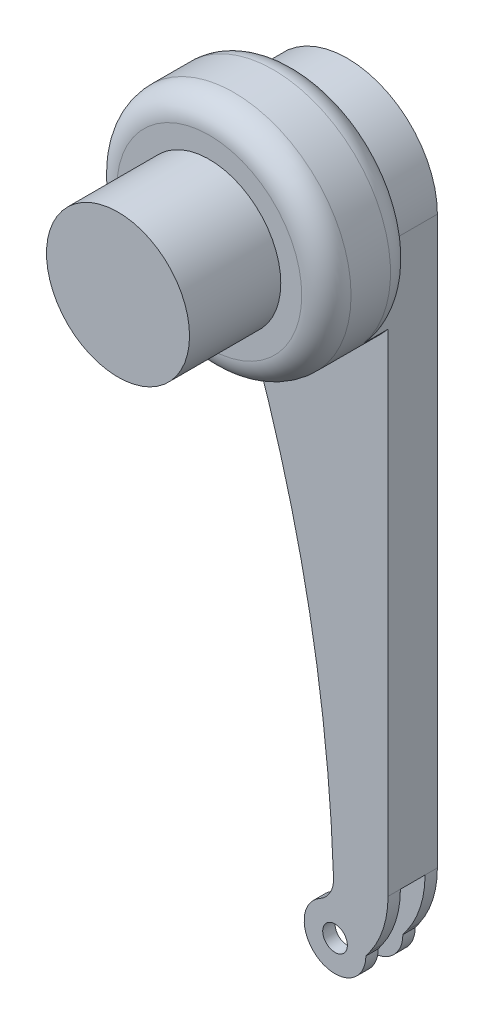
SolidWorks part; units mm, degrees
ref_plane "Front Plane" through (0, 0, 0) normal (0, 0, 1) x (1, 0, 0)
ref_plane "Top Plane" through (0, 0, 0) normal (0, 1, 0) x (1, 0, 0)
ref_plane "Right Plane" through (0, 0, 0) normal (1, 0, 0) x (0, 0, -1)
sketch "Sketch1" plane through (0, 0, 0) normal (0, 0, 1) x (1, 0, 0)
  circle A0 centre (0, 0) radius 47.5
extrude "Boss-Extrude1" add sketch "Sketch1" along normal blind 36
sketch "Sketch2" plane through (0, 0, 0) normal (0, 0, -1) x (-1, 0, 0)
  line L0 (0, 0) -> (0, -36.5) construction
  line L1 (0, -255) -> (-15, -255) construction
  line L2 (-29.1731, -252.631) -> (-27.5, -255)
  line L3 (0, -244.9103) -> (0, -255) construction
  line L4 (-36.5, 0) -> (-36.5, -229.5557)
  arc A0 (36.5, -0.0228) -> (-36.5, 0) centre (0, 0) ccw
  arc A1 (-27.5, -255) -> (-8.8693, -244.1067) centre (-15, -255) ccw
  arc A3 (-29.1731, -252.631) -> (-36.5, -229.5557) centre (3.5, -229.5557) cw
  arc A4 (-14.3935, -234.1239) -> (-8.8693, -244.1067) centre (-3.5402, -234.6378) ccw
  spline S0 degree 3 poles (36.5, -0.0228) (37.9578, -27.6639) (-9.3418, -94.6674) (-14.3935, -234.1239) knots 0 0 0 0 0.878387 0.878387 0.878387 0.878387
  dimension "D1" = 255
  dimension "D3" = 40
  dimension "D4" = 73
  dimension "D2" = 15
extrude "Boss-Extrude2" add sketch "Sketch2" along normal blind 20
sketch "Sketch3" plane through (0, 0, 36) normal (0, 0, 1) x (1, 0, 0)
  circle A0 centre (0, 0) radius 29
extrude "Boss-Extrude3" add sketch "Sketch3" along normal blind 37
fillet "Fillet1" radius 10 1 edges at (-7.1112, 46.9647, 0)
fillet "Fillet2" radius 10 1 edges at (47.5, 0, 36)
sketch "Sketch4" plane through (0, 0, -20) normal (0, 0, -1) x (-1, 0, 0)
  circle A0 centre (-15, -255) radius 5
  arc A1 (-27.5, -255) -> (-8.8693, -244.1067) centre (-15, -255) ccw construction
extrude "Cut-Extrude1" cut sketch "Sketch4" against normal blind 44
sketch "Sketch5" plane through (0, 0, 0) normal (1, 0, 0) x (0, 0, -1)
  line L0 (20, -229.5557) -> (0, -229.5557) construction
  line L1 (5, -229.5557) -> (15, -229.5557)
  line L2 (5, -229.5557) -> (5, -269.5081)
  line L3 (5, -269.5081) -> (15, -269.5081)
  line L4 (15, -229.5557) -> (15, -269.5081)
  line L5 (20, -252.631) -> (20, -229.5557) construction
  dimension "D1" = 10
  dimension "D2" = 5
extrude "Cut-Extrude2" cut sketch "Sketch5" along normal blind 102
